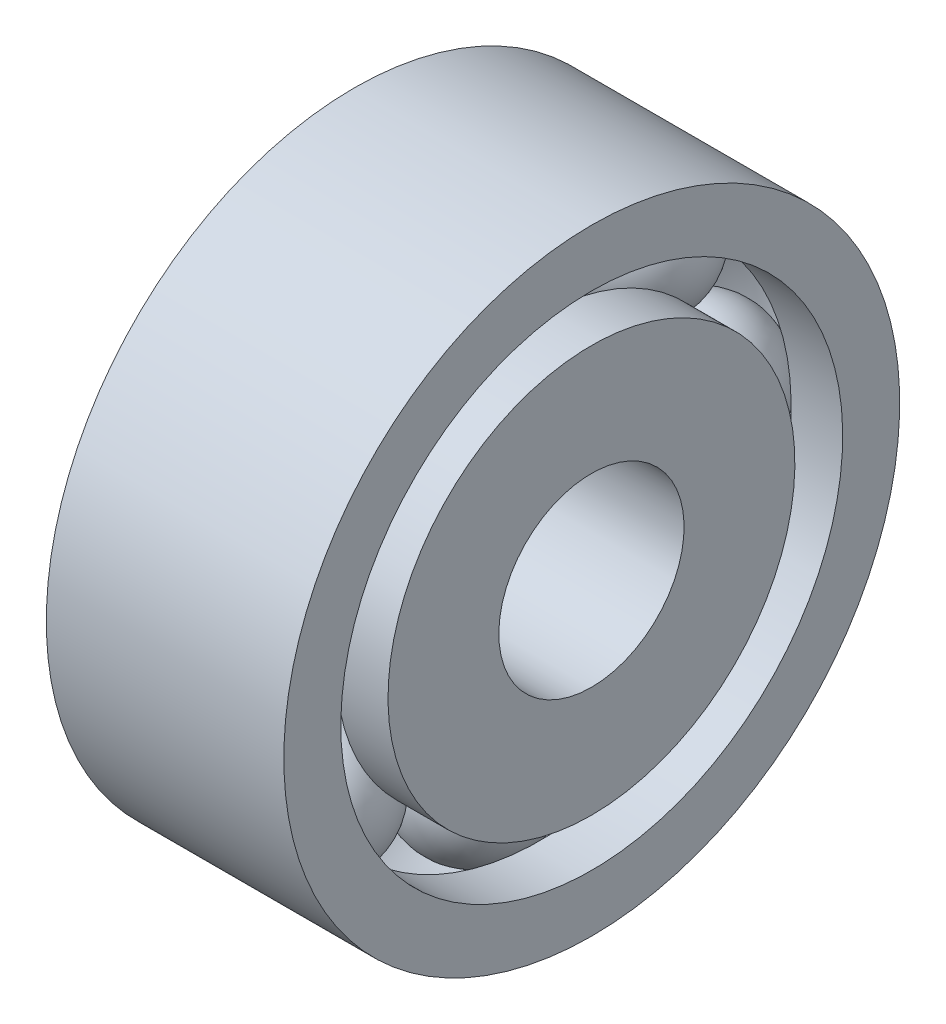
SolidWorks part; units mm, degrees
material "AISI 18-8"
ref_plane "Front Plane" through (0, 0, 0) normal (0, 0, 1) x (1, 0, 0)
ref_plane "Top Plane" through (0, 0, 0) normal (0, 1, 0) x (1, 0, 0)
ref_plane "Right Plane" through (0, 0, 0) normal (1, 0, 0) x (0, 0, -1)
sketch "Sketch1" plane through (0, 0, 0) normal (0, 0, 1) x (1, 0, 0)
  line L0 (-6.3338, 0) -> (14.2055, 0) construction
  line L1 (-6.3338, 12.1485) -> (-6.3338, 16.4665)
  line L2 (-6.3338, 16.4665) -> (6.3662, 16.4665)
  line L3 (6.3662, 16.4665) -> (6.3662, 12.1485)
  line L4 (-6.3338, 12.1485) -> (6.3662, 12.1485)
  line L5 (-4.8435, 13.4185) -> (-4.8435, 12.1485) construction
  line L6 (-4.8435, 12.1485) -> (-4.8435, 11.4178) construction
  line L7 (-4.8435, 11.4178) -> (-3.7938, 12.1485) construction
  line L8 (-4.8435, 11.4178) -> (-5.8932, 12.1485) construction
  line L9 (0.0162, 15.9585) -> (0.0162, 12.1485) construction
  line L10 (-6.3338, 13.4185) -> (6.3662, 13.4185)
  line L11 (0.0162, 12.1485) -> (0, 0) construction
  circle A1 centre (0.0162, 12.1485) radius 3.81
  spline S0 degree 2 poles (-3.7938, 12.1485) (-4.8435, 14.6885) (-5.8932, 12.1485) knots 0 0 0 1 1 1
  spline S1 degree 2 poles (3.8262, 12.1485) (4.876, 14.6885) (5.9257, 12.1485) knots 0 0 0 1 1 1
  point P6 (3.9359, 0)
  dimension "D1" = 7.62
  dimension "D2" = 12.7
  dimension "D4" = 12.1485
  dimension "D5" = 1.27
  dimension "D6" = 4.318
revolve "Revolve1" add sketch "Sketch1" angle 360 about L0 region at (-6.2032, 14.9425, 0) reverse direction yes
sketch "Sketch4" plane through (0, 0, 0) normal (0, 0, 1) x (1, 0, 0)
  line L3 (-6.35, 4.953) -> (-6.35, 10.8785)
  line L5 (6.35, 10.8785) -> (6.35, 4.953)
  line L6 (0, 12.1485) -> (0, 0) construction
  line L7 (6.35, 0) -> (-6.35, 0) construction
  line L9 (-6.35, 4.953) -> (6.35, 4.953)
  line L12 (-6.35, 10.8785) -> (6.35, 10.8785)
  line L13 (-6.35, 10.8785) -> (-6.35, 4.953)
  line L21 (6.35, 10.8785) -> (6.35, 4.953)
  circle A1 centre (0, 12.1485) radius 3.81
  point P13 (0, 0)
  dimension "D3" = 7.62
  dimension "D1" = 12.1485
  dimension "D2" = 1.27
  dimension "D4" = 4.953
  dimension "D5" = 5.9255
  dimension "D7" = 12.7
revolve "Revolve2" add sketch "Sketch4" angle 360 about L7 region at (0, 7.5053, 0) reverse direction yes
sketch "Sketch5" plane through (0, 0, 0) normal (0, 0, 1) x (1, 0, 0)
  line L0 (0, 0) -> (0, 12.1485) construction
  line L2 (0, 8.529) -> (0, 15.768)
  arc A0 (0, 8.529) -> (0, 15.768) centre (0, 12.1485) ccw
  dimension "D2" = 7.239
  dimension "D1" = 12.1485
revolve "Revolve5" add sketch "Sketch5" angle 360 about L0
pattern_circular "CirPattern2" count 8 over 360 about axis through (6.35, 0, 0) along (-1, 0, 0) of bodies 104
